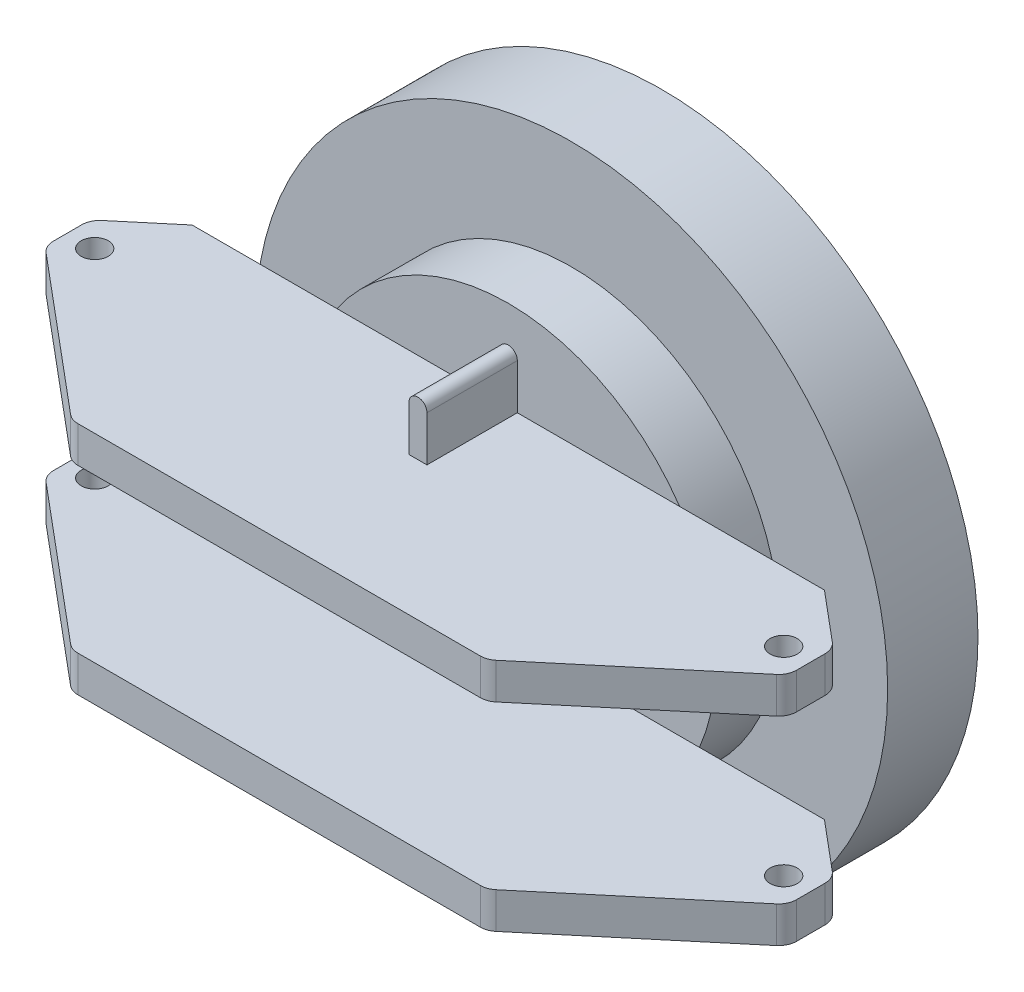
SolidWorks part; units mm, degrees
ref_plane "Front Plane" through (0, 0, 0) normal (0, 0, 1) x (1, 0, 0)
ref_plane "Top Plane" through (0, 0, 0) normal (0, 1, 0) x (1, 0, 0)
ref_plane "Right Plane" through (0, 0, 0) normal (1, 0, 0) x (0, 0, -1)
sketch "Sketch1" plane through (0, 0, 0) normal (0, 0, 1) x (1, 0, 0)
  circle A0 centre (0, 0) radius 35
extrude "Boss-Extrude1" add sketch "Sketch1" along normal blind 10
sketch "Sketch2" plane through (0, 0, 10) normal (0, 0, 1) x (1, 0, 0)
  circle A0 centre (0, 0) radius 23
  dimension "D1" = 46
extrude "Boss-Extrude2" add sketch "Sketch2" along normal blind 7
ref_plane "Plane1" through (0, 13, 0) normal (0, 1, 0) x (1, 0, 0)
sketch "Sketch3" plane through (0, 13, 0) normal (0, 1, 0) x (1, 0, 0)
  line L0 (0, -17) -> (-25.9491, -17) construction
  line L1 (-23, -17) -> (23, -17) construction
  line L2 (0, -17) -> (0, -42.3655) construction
  line L3 (-23, -17) -> (-23, -42.3655) construction
  line L4 (-23, -10) -> (-23, -17) construction
  line L5 (35, -17) -> (-35, -17)
  line L6 (-35, -17) -> (-41.1353, -22.1481)
  line L7 (-41.1353, -22.1481) -> (-41.1353, -27.1481)
  line L8 (-41.1353, -27.1481) -> (-23, -42.3655)
  line L9 (-23, -42.3655) -> (23, -42.3655)
  line L10 (41.1353, -27.1481) -> (23, -42.3655)
  line L11 (41.1353, -22.1481) -> (41.1353, -27.1481)
  line L12 (35, -17) -> (41.1353, -22.1481)
  dimension "D1" = 35
  dimension "D2" = 5
  dimension "D3" = 40
  dimension "D4" = 50
extrude "Boss-Extrude3" add sketch "Sketch3" against normal blind 4
sketch "Sketch4" plane through (0, 13, 0) normal (0, 1, 0) x (1, 0, 0)
  line L0 (-41.1353, -22.1481) -> (-41.1353, -27.1481) construction
  line L2 (0, -23.301) -> (0, 23.301) construction
  circle A0 centre (-38.1353, -24.6481) radius 1.5
  circle A1 centre (38.1353, -24.6481) radius 1.5
  dimension "D1" = 3
extrude "Cut-Extrude1" cut sketch "Sketch4" against normal blind 4
fillet "Fillet1" radius 2 6 edges at (41.1353, 11, 22.1481) (41.1353, 11, 27.1481) (23, 11, 42.3655) (-23, 11, 42.3655) (-41.1353, 11, 27.1481) (-41.1353, 11, 22.1481)
mirror "Mirror1" about plane through (0, 0, 0) normal (0, 1, 0) of "Cut-Extrude1", "Fillet1", "Boss-Extrude3"
sketch "Sketch5" plane through (0, 0, 17) normal (0, 0, 1) x (1, 0, 0)
  line L0 (0, 13) -> (0, 19) construction
  line L1 (18.9737, 13) -> (-18.9737, 13) construction
  line L2 (1, 19) -> (-1, 19)
  line L3 (-1, 19) -> (-1, 13)
  line L4 (-1, 13) -> (1, 13)
  line L5 (1, 19) -> (1, 13)
  dimension "D1" = 1
  dimension "D2" = 6
extrude "Boss-Extrude4" add sketch "Sketch5" along normal blind 10
fillet "Fillet2" 2 edges at (-1, 19, 22) (1, 19, 22) type full round first side face at (-1, 16, 22) second side face at (1, 16, 22) middle face at (0, 19, 22)
mirror "Mirror2" about plane through (0, 0, 0) normal (0, 1, 0) of "Boss-Extrude4", "Fillet2"
sketch "Sketch6" plane through (0, 0, 0) normal (0, 0, -1) x (-1, 0, 0)
  circle A0 centre (0, 0) radius 15
  dimension "D1" = 30
extrude "Cut-Extrude2" cut sketch "Sketch6" against normal blind 10
